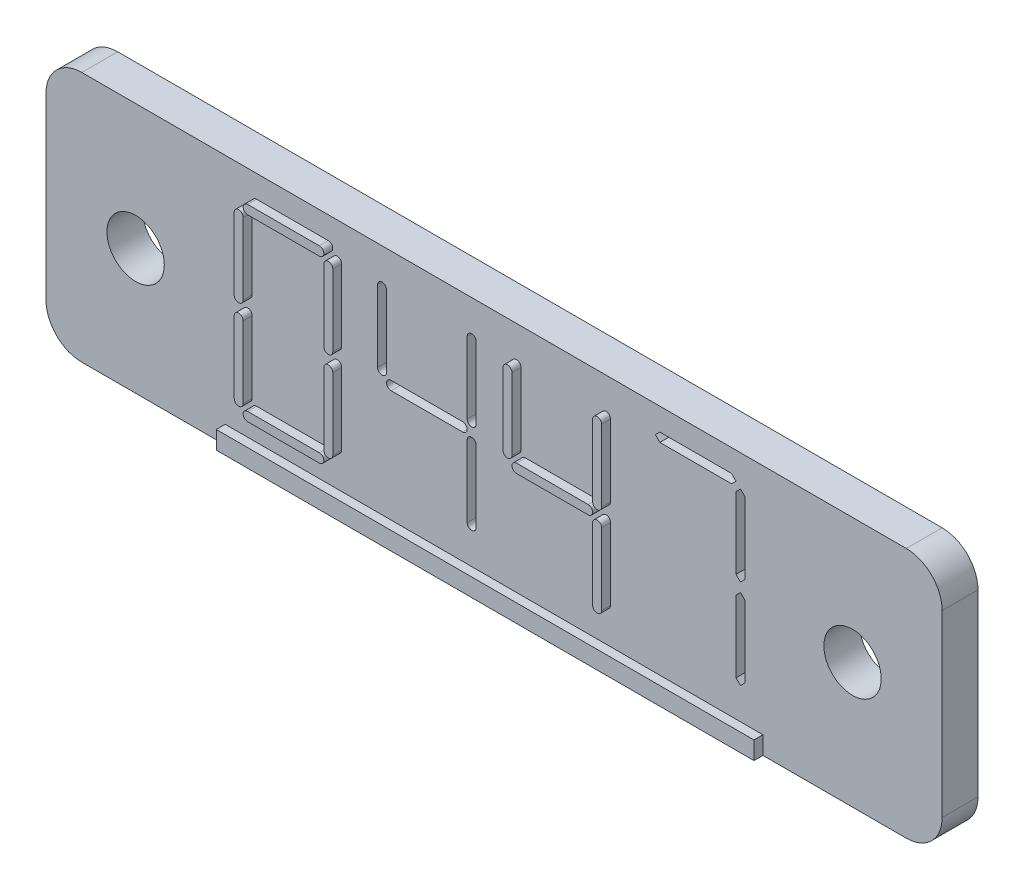
SolidWorks part; units mm, degrees
ref_plane "Front Plane" through (0, 0, 0) normal (0, 0, 1) x (1, 0, 0)
ref_plane "Top Plane" through (0, 0, 0) normal (0, 1, 0) x (1, 0, 0)
ref_plane "Right Plane" through (0, 0, 0) normal (1, 0, 0) x (0, 0, -1)
sketch "Sketch2" plane through (0, 0, 0) normal (0, 0, 1) x (1, 0, 0)
  line L1 (-25, -7) -> (25, -7)
  line L2 (-25, -7) -> (-25, 7)
  line L3 (-25, 7) -> (25, 7)
  line L4 (25, -7) -> (25, 7)
  line L5 (0, 7) -> (0, -7) construction
  line L6 (-25, 0) -> (25, 0) construction
  point P0 (0, 0)
  dimension "D1" = 50
  dimension "D2" = 14
extrude "Boss-Extrude1" add sketch "Sketch2" along normal blind 2.5
sketch "Sketch4" plane through (0, 0, 2.5) normal (0, 0, 1) x (1, 0, 0)
  line L0 (15, -6) -> (15, -7)
  line L1 (15, -6) -> (-15, -6)
  line L2 (15, -7) -> (-15, -7)
  line L3 (-15, -6) -> (-15, -7)
  line L4 (15, -6) -> (-15, -7) construction
  line L5 (15, -7) -> (-15, -6) construction
  point P0 (0, -7)
  point P1 (0, -6.5)
  point P2 (-15, -6.5)
  dimension "D1" = 0.5
  dimension "D2" = 15
extrude "Cut-Extrude1" cut sketch "Sketch4" against normal blind 0.5 flip side to cut
sketch "Sketch5" plane through (0, 0, 2) normal (0, 0, 1) x (1, 0, 0)
  line L0 (-20, 7) -> (-20, -7) construction
  line L1 (25, 7) -> (-25, 7) construction
  line L2 (-25, -7) -> (-15, -7) construction
  line L3 (-25, 7) -> (-25, -7) construction
  line L4 (20, 7) -> (20, -7) construction
  line L5 (15, -7) -> (25, -7) construction
  line L6 (25, -7) -> (25, 7) construction
  circle A0 centre (-20, 0) radius 1.6
  circle A1 centre (20, 0) radius 1.6
  dimension "D2" = 3.2
  dimension "D4" = 3.2
  dimension "D1" = 5
  dimension "D3" = 5
extrude "Cut-Extrude2" cut sketch "Sketch5" against normal blind 2
fillet "Fillet2" radius 2 4 edges at (-25, -7, 1) (25, -7, 1) (25, 7, 1) (-25, 7, 1)
sketch "Sketch6" plane through (0, 0, 2) normal (0, 0, 1) x (1, 0, 0)
  line L0 (-15, -6) -> (-15, 7) construction
  line L1 (23, 7) -> (-23, 7) construction
  line L2 (15, -6) -> (15, 7) construction
  line L3 (-9, 1) -> (-9, 5)
  line L4 (0, 7) -> (0, -6) construction
  line L5 (15, -6) -> (-15, -6) construction
  line L6 (7.5, 7) -> (7.5, -6) construction
  line L7 (-7.5, 7) -> (-7.5, -6) construction
  line L8 (15, -6) -> (-15, -6) construction
  line L9 (-15, -4.5) -> (15, -4.5) construction
  line L10 (-15, 5.5) -> (15, 5.5) construction
  line L11 (-13.75, 5.5) -> (-13.75, -4.5) construction
  line L12 (-8.75, 5.5) -> (-8.75, -4.5) construction
  line L13 (-6.25, 5.5) -> (-6.25, -4.5) construction
  line L14 (-1.25, 5.5) -> (-1.25, -4.5) construction
  line L15 (1.25, 5.5) -> (1.25, -4.5) construction
  line L16 (6.25, 5.5) -> (6.25, -4.5) construction
  line L17 (8.75, 5.5) -> (8.75, -4.5) construction
  line L18 (13.75, 5.5) -> (13.75, -4.5) construction
  line L19 (-15, 0.5) -> (15, 0.5) construction
  line L20 (-13.25, -4.25) -> (-9.25, -4.25)
  line L21 (-13.25, 5.75) -> (-9.25, 5.75)
  line L22 (-13.25, 5.75) -> (-13.25, 5.25) construction
  line L23 (-13.25, 5.25) -> (-9.25, 5.25)
  line L24 (-9.25, 5.75) -> (-9.25, 5.25) construction
  line L25 (-11.25, 5.25) -> (-11.25, 5.75) construction
  line L26 (-13.25, 5.5) -> (-9.25, 5.5) construction
  line L27 (-9.25, -4.75) -> (-9.25, -4.25) construction
  line L28 (-13.25, -4.75) -> (-9.25, -4.75)
  line L29 (-13.25, -4.75) -> (-13.25, -4.25) construction
  line L30 (-13.5, 0) -> (-13.5, -4)
  line L31 (-14, 1) -> (-13.5, 1) construction
  line L32 (-14, 1) -> (-14, 5)
  line L33 (-14, 5) -> (-13.5, 5) construction
  line L34 (-13.5, 1) -> (-13.5, 5)
  line L35 (-13.75, 5) -> (-13.75, 1) construction
  line L36 (-14, 3) -> (-13.5, 3) construction
  line L37 (-14, 0) -> (-14, -4)
  line L38 (-14, 0) -> (-13.5, 0) construction
  line L39 (-14, -4) -> (-13.5, -4) construction
  line L40 (-9, 1) -> (-8.5, 1) construction
  line L41 (-8.5, 1) -> (-8.5, 5)
  line L42 (-9, 5) -> (-8.5, 5) construction
  line L43 (-9, 0) -> (-8.5, 0) construction
  line L44 (-8.5, 0) -> (-8.5, -4)
  line L45 (-9, -4) -> (-8.5, -4) construction
  line L46 (-9, 0) -> (-9, -4)
  line L51 (-5.75, 0.75) -> (-5.75, 0.25) construction
  line L52 (-5.75, 0.75) -> (-1.75, 0.75)
  line L53 (-1.75, 0.75) -> (-1.75, 0.25) construction
  line L54 (-5.75, 0.25) -> (-1.75, 0.25)
  line L59 (-13.25, 0.75) -> (-13.25, 0.25) [skipped]
  line L60 (-13.25, 0.25) -> (-9.25, 0.25) [skipped]
  line L61 (-9.25, 0.75) -> (-9.25, 0.25) [skipped]
  line L62 (-13.25, 0.75) -> (-9.25, 0.75) [skipped]
  line L63 (-5.75, 5.75) -> (-5.75, 5.25) [skipped]
  line L64 (-5.75, 5.25) -> (-1.75, 5.25) [skipped]
  line L65 (-1.75, 5.75) -> (-1.75, 5.25) [skipped]
  line L66 (-5.75, 5.75) -> (-1.75, 5.75) [skipped]
  line L67 (-6, 1) -> (-6.5, 1) construction
  line L68 (-6.5, 1) -> (-6.5, 5)
  line L69 (-6, 5) -> (-6.5, 5) construction
  line L70 (-6, 1) -> (-6, 5)
  line L71 (-1, 0) -> (-1.5, 0) construction
  line L72 (-1, 0) -> (-1, -4)
  line L73 (-1, -4) -> (-1.5, -4) construction
  line L74 (-1.5, 0) -> (-1.5, -4)
  line L75 (-1, 5) -> (-1.5, 5) construction
  line L76 (-1.5, 1) -> (-1.5, 5)
  line L77 (-1, 1) -> (-1.5, 1) construction
  line L78 (-1, 1) -> (-1, 5)
  line L95 (14, 0) -> (13.5, 0) construction
  line L96 (14, 0) -> (14, -4)
  line L97 (14, -4) -> (13.5, -4) construction
  line L98 (13.5, 0) -> (13.5, -4)
  line L99 (13.25, 5.25) -> (9.25, 5.25)
  line L100 (9.25, 5.75) -> (9.25, 5.25) construction
  line L101 (13.25, 5.75) -> (9.25, 5.75)
  line L102 (13.25, 5.75) -> (13.25, 5.25) construction
  line L103 (14, 5) -> (13.5, 5) construction
  line L104 (13.5, 1) -> (13.5, 5)
  line L105 (14, 1) -> (13.5, 1) construction
  line L106 (14, 1) -> (14, 5)
  line L107 (1.5, 1) -> (1.5, 5)
  line L108 (1, 1) -> (1, 5)
  line L109 (1.75, 0.25) -> (5.75, 0.25)
  line L110 (1.75, 0.75) -> (5.75, 0.75)
  line L111 (6.5, 1) -> (6.5, 5)
  line L112 (6, 1) -> (6, 5)
  line L113 (6.5, 0) -> (6.5, -4)
  line L114 (6, 0) -> (6, -4)
  line L115 (9.25, 5.75) -> (9, 5.5)
  line L116 (9, 5.5) -> (9.25, 5.25)
  line L117 (13.25, 5.75) -> (13.5, 5.5)
  line L118 (13.5, 5.5) -> (13.25, 5.25)
  line L119 (13.5, 5) -> (13.75, 5.25)
  line L120 (13.75, 5.25) -> (14, 5)
  line L121 (13.5, 1) -> (13.75, 0.75)
  line L122 (13.75, 0.75) -> (14, 1)
  line L123 (13.5, 0) -> (13.75, 0.25)
  line L124 (13.75, 0.25) -> (14, 0)
  line L125 (14, -4) -> (13.75, -4.25)
  line L126 (13.75, -4.25) -> (13.5, -4)
  arc A0 (-14, 5) -> (-13.5, 5) centre (-13.75, 5) cw
  arc A1 (-13.25, 5.25) -> (-13.25, 5.75) centre (-13.25, 5.5) cw
  arc A2 (-9.25, 5.75) -> (-9.25, 5.25) centre (-9.25, 5.5) cw
  arc A3 (-9, 5) -> (-8.5, 5) centre (-8.75, 5) cw
  arc A4 (-8.5, 1) -> (-9, 1) centre (-8.75, 1) cw
  arc A5 (-9, 0) -> (-8.5, 0) centre (-8.75, 0) cw
  arc A6 (-14, 1) -> (-13.5, 1) centre (-13.75, 1) ccw
  arc A7 (-8.5, -4) -> (-9, -4) centre (-8.75, -4) cw
  arc A8 (-9.25, -4.25) -> (-9.25, -4.75) centre (-9.25, -4.5) cw
  arc A9 (-13.25, -4.75) -> (-13.25, -4.25) centre (-13.25, -4.5) cw
  arc A10 (-13.5, -4) -> (-14, -4) centre (-13.75, -4) cw
  arc A11 (-5.75, 0.25) -> (-5.75, 0.75) centre (-5.75, 0.5) cw
  arc A12 (-6.5, 1) -> (-6, 1) centre (-6.25, 1) ccw
  arc A13 (-1.75, 0.75) -> (-1.75, 0.25) centre (-1.75, 0.5) cw
  arc A14 (-1.5, 0) -> (-1, 0) centre (-1.25, 0) cw
  arc A15 (-1.5, 1) -> (-1, 1) centre (-1.25, 1) ccw
  arc A16 (-1.5, -4) -> (-1, -4) centre (-1.25, -4) ccw
  arc A17 (-6.5, 5) -> (-6, 5) centre (-6.25, 5) cw
  arc A18 (-1.5, 5) -> (-1, 5) centre (-1.25, 5) cw
  arc A19 (1, 5) -> (1.5, 5) centre (1.25, 5) cw
  arc A20 (1, 1) -> (1.5, 1) centre (1.25, 1) ccw
  arc A21 (1.75, 0.25) -> (1.75, 0.75) centre (1.75, 0.5) cw
  arc A22 (5.75, 0.75) -> (5.75, 0.25) centre (5.75, 0.5) cw
  arc A23 (6, 1) -> (6.5, 1) centre (6.25, 1) ccw
  arc A24 (6, 5) -> (6.5, 5) centre (6.25, 5) cw
  arc A25 (6, 0) -> (6.5, 0) centre (6.25, 0) cw
  arc A26 (6, -4) -> (6.5, -4) centre (6.25, -4) ccw
  arc A27 (-14, 0) -> (-13.5, 0) centre (-13.75, 0) cw
  point P40 (-11.25, 5.5)
  point P48 (-13.75, 3)
  dimension "D1" = 7.5
  dimension "D2" = 7.5
  dimension "D3" = 7.5
  dimension "D4" = 1.5
  dimension "D5" = 1.5
  dimension "D6" = 1.25
  dimension "D7" = 1.25
  dimension "D8" = 2.5
  dimension "D9" = 4
  dimension "D10" = 0.5
  dimension "D11" = 2.5
  dimension "D12" = 4
  dimension "D13" = 0.5
  dimension "D15" = 0.25
  dimension "D18" = 0.25
  dimension "D19" = 4
  dimension "D20" = 0.5
  dimension "D22" = 0.25
  dimension "D23" = 0.5
  dimension "D14" = 0.5
  dimension "D24" = 0.5
  dimension "D16" = 2
  dimension "D17" = 2
  dimension "D21" = 2
extrude "Cut-Extrude7" cut sketch "Sketch6" against normal blind 0.5 contours L70 A17 L68 A12 | A14 L72 A16 L74 | L54 A13 L52 A11 | A18 L78 A15 L76 | L116 L99 L118 L117 L101 L115 | L123 L124 L96 L125 L126 L98 | L119 L120 L106 L122 L121 L104
extrude "Boss-Extrude4" add sketch "Sketch6<10>" along normal blind 0.5 contours L20 A8 L28 A9 | L23 A2 L21 A1 | A10 L37 A27 L30 | A5 L44 A7 L46 | A3 L41 A4 L3 | L34 A0 L32 A6 | A19 L107 A20 L108 | A25 L113 A26 L114 | A21 L110 A22 L109 | A23 L111 A24 L112
sketch "Sketch6<10>" plane through (0, 0, 2) normal (0, 0, 1) x (1, 0, 0) same geometry as "Sketch6"
